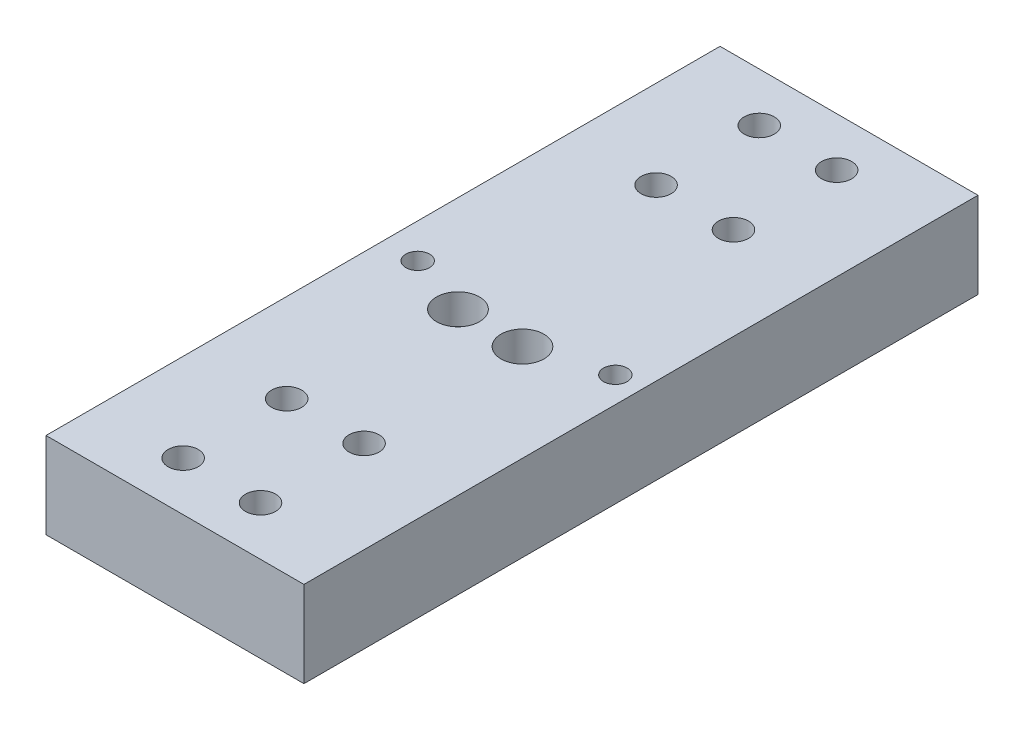
SolidWorks part; units mm, degrees
ref_plane "Front Plane" through (0, 0, 0) normal (0, 0, 1) x (1, 0, 0)
ref_plane "Top Plane" through (0, 0, 0) normal (0, 1, 0) x (1, 0, 0)
ref_plane "Right Plane" through (0, 0, 0) normal (1, 0, 0) x (0, 0, -1)
sketch "Sketch3" plane through (-27.527, 0, 0) normal (0, 1, 0) x (0, 0, 1)
  line L0 (41.3041, 73.5608) -> (-72.5469, 73.5608) construction
  line L2 (41.3041, 8.3895) -> (-72.5469, 8.3895) construction
  line L3 (31.3041, -26.6984) -> (31.3041, 62.3179) construction
  line L5 (-78.6959, -26.6984) -> (-78.6959, 62.3179) construction
  line L7 (31.3041, 62.3179) -> (-78.6959, -26.6984) construction
  line L13 (54.6906, 47.8098) -> (-102.0824, 47.8098)
  line L14 (54.6906, 47.8098) -> (54.6906, -12.1902)
  line L15 (54.6906, -12.1902) -> (-102.0824, -12.1902)
  line L16 (-102.0824, 47.8098) -> (-102.0824, -12.1902)
  line L17 (54.6906, 47.8098) -> (-102.0824, -12.1902) construction
  line L18 (54.6906, -12.1902) -> (-102.0824, 47.8098) construction
  point P2 (-23.6959, 17.8098)
  dimension "D1" = 60
extrude "Boss-Extrude6" add sketch "Sketch3" along normal blind 20
sketch "Sketch4" plane through (0, 20, 0) normal (0, 1, 0) x (1, 0, 0)
  line L0 (20.2828, 23.6959) -> (-39.7172, 23.6959) construction
  line L1 (20.2828, -54.6906) -> (20.2828, 102.0824) construction
  line L2 (-39.7172, 102.0824) -> (-39.7172, -54.6906) construction
  line L3 (20.2828, -31.3041) -> (-39.7172, -31.3041) construction
  line L4 (20.2828, 78.6959) -> (-39.7172, 78.6959) construction
  line L5 (-10.2465, -54.6906) -> (-9.7172, 102.0824) construction
  line L6 (-39.7172, -54.6906) -> (20.2828, -54.6906) construction
  line L7 (20.2828, 102.0824) -> (-39.7172, 102.0824) construction
  line L8 (20.2828, -43.3041) -> (-39.7172, -43.3041) construction
  line L9 (20.2828, -19.3041) -> (-39.7172, -19.3041) construction
  line L10 (-39.7172, 66.6959) -> (20.2828, 66.6959) construction
  line L11 (-39.7172, 90.6959) -> (20.2828, 90.6959) construction
  line L12 (-19.2081, -43.3041) -> (-19.2081, 106.6241) construction
  line L13 (-1.208, -43.3041) -> (-1.208, 116.9979) construction
  circle A2 centre (-1.127, -19.3041) radius 2.25
  circle A3 centre (-19.1271, -19.3041) radius 2.25
  circle A4 centre (-1.208, -43.3041) radius 2.25
  circle A5 centre (-19.2081, -43.3041) radius 2.25
  circle A6 centre (-19.2081, 66.6959) radius 2.25
  circle A7 centre (-19.2081, 90.6959) radius 2.25
  circle A8 centre (-1.208, 90.6959) radius 2.25
  circle A9 centre (-1.208, 66.6959) radius 2.25
  dimension "D5" = 9
  dimension "D9" = 4.5
  dimension "D12" = 4.5
  dimension "D1" = 55
  dimension "D2" = 55
  dimension "D3" = 12
  dimension "D4" = 12
  dimension "D6" = 9
  dimension "D7" = 9
  dimension "D8" = 9
  dimension "D10" = 12
  dimension "D11" = 12
extrude "Cut-Extrude1" cut sketch "Sketch4" against normal up to next
sketch "Sketch6" plane through (0, 20, 0) normal (0, 1, 0) x (1, 0, 0)
  line L3 (-9.7172, -54.6906) -> (-9.7172, 102.0824) construction
  line L4 (-39.7172, -54.6906) -> (20.2828, -54.6906) construction
  line L5 (20.2828, 102.0824) -> (-39.7172, 102.0824) construction
  line L6 (-17.2172, 18.6316) -> (-2.2172, 18.6316) construction
  circle A0 centre (-17.2172, 18.6316) radius 3.25
  circle A1 centre (-2.2172, 18.6316) radius 3.25
  point P0 (-9.7172, 18.6316)
  dimension "D1" = 6.5
  dimension "D2" = 6.5
  dimension "D3" = 15
  dimension "D4" = 73.3222
extrude "Cut-Extrude2" cut sketch "Sketch6" against normal up to next
sketch "Sketch7" plane through (0, 20, 0) normal (0, 1, 0) x (1, 0, 0)
  circle A0 centre (-19.1271, -19.3041) radius 3.5
  circle A1 centre (-19.2081, -43.3041) radius 3.5
  circle A2 centre (-1.208, -43.3041) radius 3.5
  circle A3 centre (-1.127, -19.3041) radius 3.5
  circle A4 centre (-1.208, 66.6959) radius 3.5
  circle A5 centre (-19.2081, 66.6959) radius 3.5
  circle A6 centre (-19.2081, 90.6959) radius 3.5
  circle A7 centre (-1.208, 90.6959) radius 3.5
  dimension "D1" = 7
extrude "Cut-Extrude3" cut sketch "Sketch7" against normal blind 5
sketch "Sketch8" plane through (0, 20, 0) normal (0, 1, 0) x (1, 0, 0)
  circle A0 centre (-17.2172, 18.6316) radius 5
  circle A1 centre (-2.2172, 18.6316) radius 5
  dimension "D1" = 10
  dimension "D2" = 10
extrude "Cut-Extrude4" cut sketch "Sketch8" against normal blind 7
sketch "Sketch9" plane through (0, 20, 0) normal (0, 1, 0) x (1, 0, 0)
  circle A0 centre (-31.6579, 23.7018) radius 2.75
  circle A1 centre (14.2827, 23.7357) radius 2.75
  dimension "D1" = 5.5
extrude "Cut-Extrude5" cut sketch "Sketch9" against normal up to next
